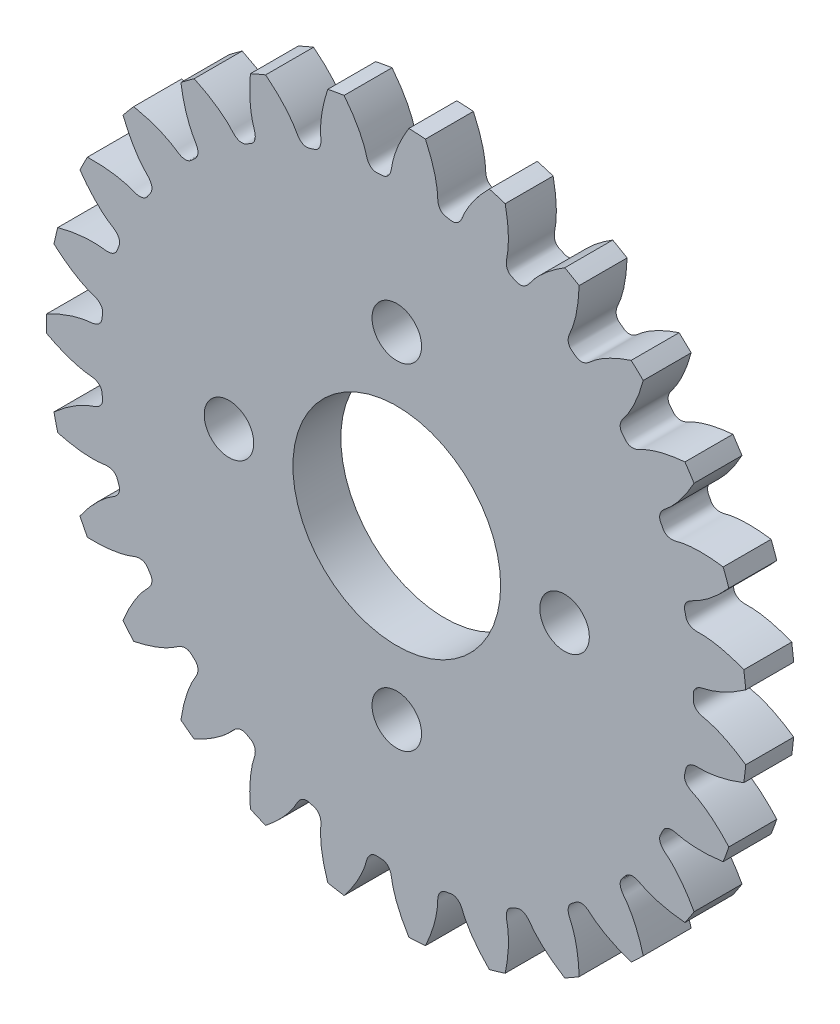
SolidWorks part; units mm, degrees
material "玻纤板"
ref_plane "前视基准面" through (0, 0, 0) normal (0, 0, 1) x (1, 0, 0)
ref_plane "上视基准面" through (0, 0, 0) normal (0, 1, 0) x (1, 0, 0)
ref_plane "右视基准面" through (0, 0, 0) normal (1, 0, 0) x (0, 0, -1)
ref_axis "基准轴1" through (0, 0, 55) along (0, 0, -1)
sketch "旋转草图小直齿轮" plane through (0, 0, 0) normal (1, 0, 0) x (0, 0, -1)
  line L0 (0, 0) -> (1, 0) construction
  line L1 (-1.5, 0) -> (-1.5, 21.93)
  line L2 (-1.5, 21.93) -> (1.5, 21.93)
  line L3 (1.5, 21.93) -> (1.5, 0)
  line L4 (1.5, 0) -> (-1.5, 0)
revolve "小直齿轮" add sketch "旋转草图小直齿轮" angle 360 about L0
sketch "齿草图小直齿轮" plane through (0, 0, 0) normal (0, 0, 1) x (1, 0, 0)
  arc A0 (21.915, 2.0856) -> (21.915, -2.0856) centre (0, 0) cw
  spline S0 degree 3 poles (21.915, -2.0856) (21.8719, -2.0547) (21.8074, -2.0092) (21.7212, -1.9498) (21.6576, -1.9066) (21.5944, -1.8644) (21.5318, -1.8232) (21.4697, -1.783) (21.4082, -1.7438) (21.3472, -1.7056) (21.2869, -1.6684) (21.2271, -1.6321) (21.1679, -1.5968) (21.1094, -1.5624) (21.0514, -1.529) (20.9941, -1.4964) (20.9374, -1.4648) (20.8814, -1.4341) (20.8261, -1.4042) (20.7714, -1.3753) (20.7174, -1.3472) (20.6641, -1.3199) (20.6115, -1.2935) (20.5597, -1.2679) (20.5085, -1.2431) (20.4581, -1.2192) (20.4084, -1.196) (20.3594, -1.1736) (20.3112, -1.152) (20.2638, -1.1311) (20.2172, -1.111) (20.1713, -1.0916) (20.1262, -1.0729) (20.0819, -1.0549) (20.0385, -1.0377) (19.9958, -1.0211) (19.954, -1.0052) (19.9129, -0.9899) (19.8728, -0.9753) (19.8334, -0.9613) (19.7949, -0.9479) (19.7573, -0.9351) (19.7205, -0.9229) (19.6846, -0.9113) (19.6496, -0.9003) (19.6155, -0.8898) (19.5822, -0.8798) (19.5499, -0.8704) (19.5184, -0.8615) (19.4879, -0.853) (19.4582, -0.8451) (19.4295, -0.8376) (19.4017, -0.8306) (19.3748, -0.824) (19.3489, -0.8179) (19.3239, -0.8121) (19.2998, -0.8068) (19.2767, -0.8018) (19.2227, -0.7907) (19.1629, -0.7792) (19.0986, -0.7621) (19.0601, -0.7506) (19.0223, -0.7381) (18.9851, -0.7242) (18.9483, -0.7089) (18.9118, -0.6918) (18.8754, -0.6728) (18.8391, -0.6514) (18.8026, -0.627) (18.7659, -0.599) (18.7291, -0.5666) (18.6926, -0.5288) (18.6571, -0.4845) (18.6236, -0.4328) (18.5941, -0.373) (18.571, -0.3055) (18.5573, -0.2353) (18.5519, -0.1326) (18.5572, 0) (18.5519, 0.1326) (18.5573, 0.2353) (18.571, 0.3055) (18.5941, 0.373) (18.6236, 0.4328) (18.6571, 0.4845) (18.6926, 0.5288) (18.7291, 0.5666) (18.7659, 0.599) (18.8026, 0.627) (18.8391, 0.6514) (18.8754, 0.6728) (18.9118, 0.6918) (18.9483, 0.7089) (18.9851, 0.7242) (19.0223, 0.7381) (19.0601, 0.7506) (19.0986, 0.7621) (19.1629, 0.7792) (19.2227, 0.7907) (19.2767, 0.8018) (19.2998, 0.8068) (19.3239, 0.8121) (19.3489, 0.8179) (19.3748, 0.824) (19.4017, 0.8306) (19.4295, 0.8376) (19.4582, 0.8451) (19.4879, 0.853) (19.5184, 0.8615) (19.5499, 0.8704) (19.5822, 0.8798) (19.6155, 0.8898) (19.6496, 0.9003) (19.6846, 0.9113) (19.7205, 0.9229) (19.7573, 0.9351) (19.7949, 0.9479) (19.8334, 0.9613) (19.8728, 0.9753) (19.9129, 0.9899) (19.954, 1.0052) (19.9958, 1.0211) (20.0385, 1.0377) (20.0819, 1.0549) (20.1262, 1.0729) (20.1713, 1.0916) (20.2172, 1.111) (20.2638, 1.1311) (20.3112, 1.152) (20.3594, 1.1736) (20.4084, 1.196) (20.4581, 1.2192) (20.5085, 1.2431) (20.5597, 1.2679) (20.6115, 1.2935) (20.6641, 1.3199) (20.7174, 1.3472) (20.7714, 1.3753) (20.8261, 1.4042) (20.8814, 1.4341) (20.9374, 1.4648) (20.9941, 1.4964) (21.0514, 1.529) (21.1094, 1.5624) (21.1679, 1.5968) (21.2271, 1.6321) (21.2869, 1.6684) (21.3472, 1.7056) (21.4082, 1.7438) (21.4697, 1.783) (21.5318, 1.8232) (21.5944, 1.8644) (21.6576, 1.9066) (21.7212, 1.9498) (21.8074, 2.0092) (21.8719, 2.0547) (21.915, 2.0856) knots 0 0 0 0 0.019049 0.028393 0.037616 0.046719 0.055701 0.064563 0.073304 0.081924 0.090424 0.098803 0.107062 0.1152 0.123217 0.131115 0.138891 0.146547 0.154082 0.161497 0.168791 0.175965 0.183018 0.18995 0.196762 0.203454 0.210024 0.216475 0.222804 0.229013 0.235102 0.24107 0.246917 0.252644 0.25825 0.263736 0.269101 0.274346 0.27947 0.284473 0.289356 0.294118 0.29876 0.303281 0.307682 0.311962 0.316122 0.320161 0.324079 0.327877 0.331554 0.335111 0.338547 0.341862 0.345057 0.348132 0.351085 0.353919 0.356631 0.370919 0.375775 0.380574 0.385337 0.390087 0.394852 0.399665 0.404567 0.409606 0.41484 0.420337 0.426175 0.432439 0.439212 0.446567 0.454538 0.463101 0.472142 0.480173 0.5 0.519827 0.527858 0.536899 0.545462 0.553433 0.560788 0.567561 0.573825 0.579663 0.58516 0.590394 0.595433 0.600335 0.605148 0.609913 0.614663 0.619426 0.624225 0.629081 0.643369 0.646081 0.648915 0.651868 0.654943 0.658138 0.661453 0.664889 0.668446 0.672123 0.675921 0.679839 0.683878 0.688038 0.692318 0.696719 0.70124 0.705882 0.710644 0.715527 0.72053 0.725654 0.730899 0.736264 0.74175 0.747356 0.753083 0.75893 0.764898 0.770987 0.777196 0.783525 0.789976 0.796546 0.803238 0.81005 0.816982 0.824035 0.831209 0.838503 0.845918 0.853453 0.861109 0.868885 0.876783 0.8848 0.892938 0.901197 0.909576 0.918076 0.926696 0.935437 0.944299 0.953281 0.962384 0.971607 0.980951 1 1 1 1
extrude "齿拉伸切除小直齿轮" cut sketch "齿草图小直齿轮" against normal blind 1.5 and the other way blind 1.5
pattern_circular "齿形小直齿轮" count 27 every 13.333 about axis through (0, 0, 55) along (0, 0, -1) of "齿拉伸切除小直齿轮"
sketch "辅助草图小直齿轮" plane through (0, 0, 0) normal (0, 0, 1) x (1, 0, 0)
  circle A0 centre (0, 0) radius 20.25 construction
  circle A1 centre (0, 0) radius 19.0288 construction
  circle A2 centre (0, 0) radius 19.2389 construction
  circle A3 centre (0, 0) radius 21.93 construction
  circle A4 centre (0, 0) radius 18.555 construction
  dimension "PitchDiameter" = 40.5
  dimension "BaseDiameter" = 38.0576
  dimension "FormDiameter" = 38.4778
  dimension "MajorDiameter" = 43.86
  dimension "MinorDiameter" = 37.11
sketch "草图5" plane through (0, 0, 1.5) normal (0, 0, 1) x (1, 0, 0)
  circle A0 centre (0, 0) radius 6.5
  circle A1 centre (0, 0) radius 10.5 construction
  circle A2 centre (0, 10.5) radius 1.55
  circle A3 centre (10.5, 0) radius 1.55
  circle A4 centre (0, -10.5) radius 1.55
  circle A5 centre (-10.5, 0) radius 1.55
  point P15 (0, 0)
  dimension "D1" = 13
  dimension "D2" = 21
  dimension "D3" = 3.1
  dimension "D4" = 4
extrude "切除-拉伸2" cut sketch "草图5" against normal blind 10
